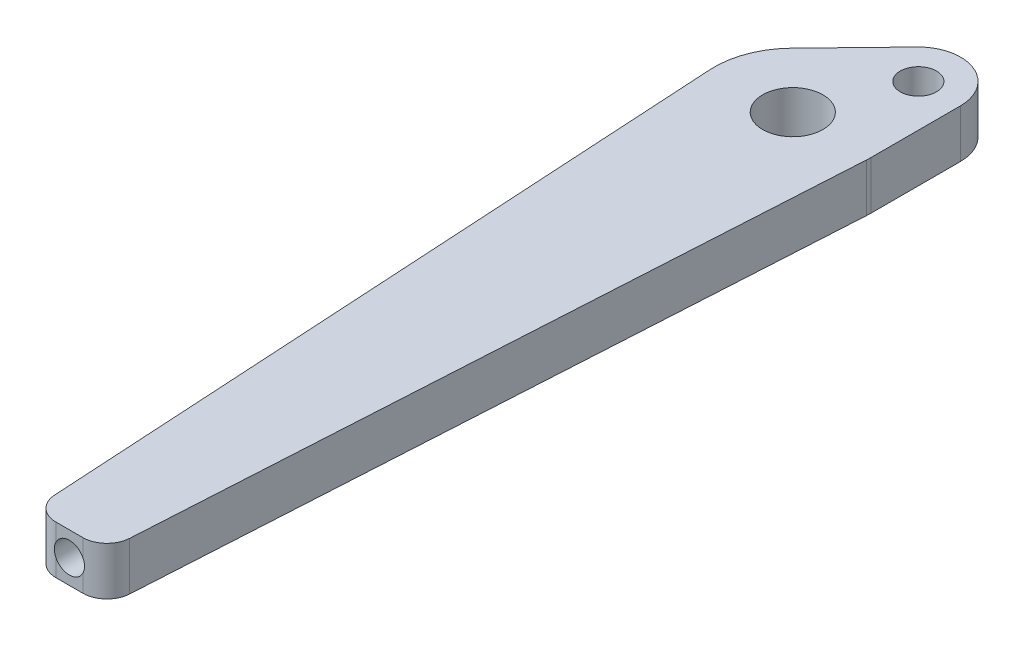
SolidWorks part; units mm, degrees
ref_plane "Front Plane" through (0, 0, 0) normal (0, 0, 1) x (1, 0, 0)
ref_plane "Top Plane" through (0, 0, 0) normal (0, 1, 0) x (1, 0, 0)
ref_plane "Right Plane" through (0, 0, 0) normal (1, 0, 0) x (0, 0, -1)
sketch "Sketch1" plane through (0, 0, 0) normal (0, 1, 0) x (1, 0, 0)
  line L0 (-5.9333, 5.7394) -> (0.6152, 12.509)
  line L1 (8.255, 9.4186) -> (8.255, 0)
  line L2 (8.2409, -0.4822) -> (3.81, -76.2)
  line L3 (-8.2409, -0.4822) -> (-3.81, -76.2)
  line L4 (-3.81, -76.2) -> (3.81, -76.2)
  line L5 (0, 0) -> (0, -76.2) construction
  circle A0 centre (0, 0) radius 3.175
  circle A1 centre (3.81, 9.4186) radius 1.905
  arc A2 (-5.9333, 5.7394) -> (-8.2409, -0.4822) centre (0, 0) ccw
  arc A3 (8.255, 9.4186) -> (0.6152, 12.509) centre (3.81, 9.4186) ccw
  arc A5 (8.2409, -0.4822) -> (8.255, 0) centre (0, 0) ccw
  dimension "D1" = 6.35
  dimension "D2" = 3.81
  dimension "D3" = 76.2
  dimension "D5" = 2.54
  dimension "D6" = 5.08
  dimension "D4" = 7.62
extrude "Boss-Extrude1" add sketch "Sketch1" along normal blind 5.08
sketch "Sketch5" plane through (0, 0, 76.2) normal (0, 0, 1) x (1, 0, 0)
  line L0 (-3.81, 2.54) -> (3.81, 2.54) construction
  line L1 (-3.81, 5.08) -> (-3.81, 0) construction
  line L2 (3.81, 5.08) -> (3.81, 0) construction
  line L3 (0, 5.08) -> (0, 0) construction
  line L4 (-3.81, 5.08) -> (3.81, 5.08) construction
  point P13 (0, 2.54)
hole_wizard "1/8 (0.125) Diameter Hole1" positions "Sketch5" profile "Sketch6" hole size "1/8" standard "ANSI Inch"
sketch "Sketch6" plane through (0, 2.54, 76.2) normal (1, 0, 0) x (0, -1, 0)
  line L0 (0, 0) -> (0, 13.6539)
  line L1 (0, 13.6539) -> (1.5875, 12.7)
  line L2 (1.5875, 12.7) -> (1.5875, 0)
  line L5 (1.5875, 0) -> (0, 0)
  line L10 (0, 13.6539) -> (-1.5875, 12.7) construction
  line L11 (0, -6.35) -> (0, 107.95) construction
  dimension "Hole Dia." = 3.175
  dimension "Hole Depth" = 12.7
  dimension "Drill Angle" = 118
fillet "Fillet1" radius 2.54 2 edges at (-3.81, 2.54, 76.2) (3.81, 2.54, 76.2)
